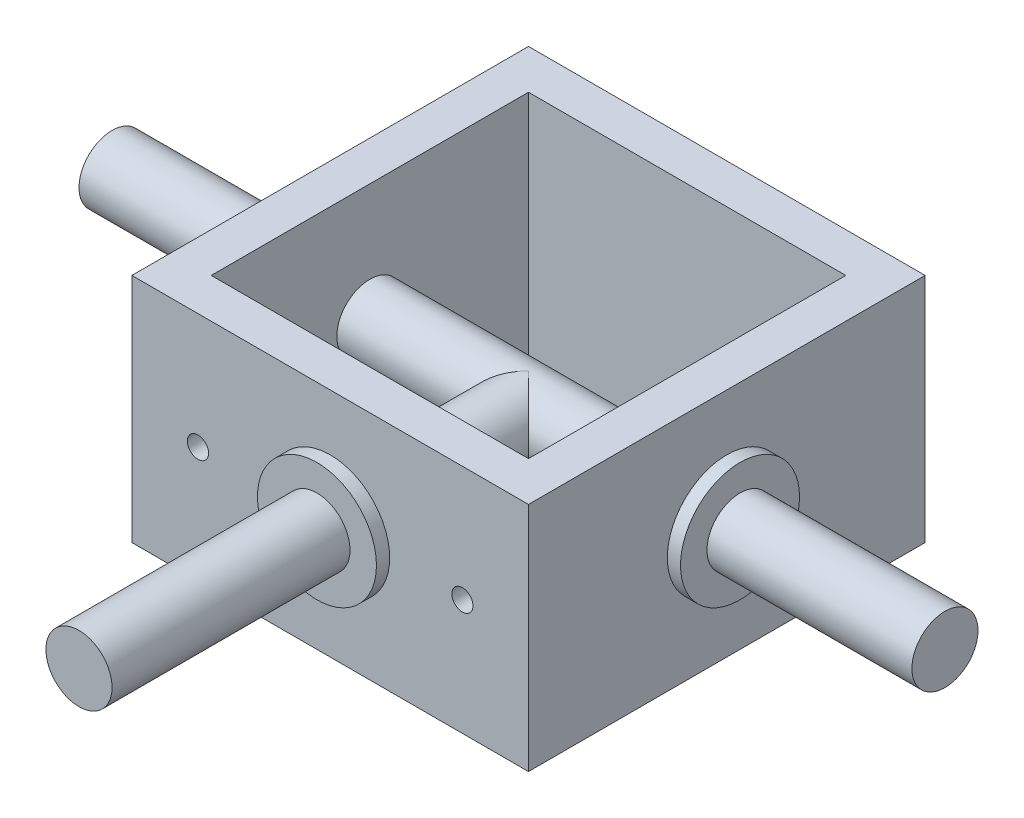
SolidWorks part; units mm, degrees
ref_plane "Alzado" through (0, 0, 0) normal (0, 0, 1) x (1, 0, 0)
ref_plane "Planta" through (0, 0, 0) normal (0, 1, 0) x (1, 0, 0)
ref_plane "Vista lateral" through (0, 0, 0) normal (1, 0, 0) x (0, 0, -1)
sketch "Croquis1" plane through (0, 0, 0) normal (0, 1, 0) x (1, 0, 0)
  line L1 (-30, 30) -> (30, 30)
  line L2 (-30, 30) -> (-30, -30)
  line L3 (-30, -30) -> (30, -30)
  line L4 (30, 30) -> (30, -30)
  line L5 (-30, 30) -> (30, -30) construction
  line L6 (-30, -30) -> (30, 30) construction
  line L7 (-24, -24) -> (24, -24)
  line L8 (-24, -24) -> (-24, 24)
  line L9 (-24, 24) -> (24, 24)
  line L10 (24, -24) -> (24, 24)
  point P0 (0, 0)
  dimension "D1" = 60
  dimension "D2" = 60
  dimension "D3" = 6
  dimension "D4" = 6
extrude "Saliente-Extruir1" add sketch "Croquis1" along normal blind 17.5 and the other way blind 17.5
sketch "Croquis2" plane through (0, 0, 30) normal (0, 0, 1) x (1, 0, 0)
  circle A0 centre (0, 0) radius 9
  dimension "D1" = 18
extrude "Saliente-Extruir2" add sketch "Croquis2" along normal blind 2
sketch "Croquis3" plane through (30, 0, 0) normal (1, 0, 0) x (0, 0, -1)
  circle A0 centre (0, 0) radius 9
  dimension "D1" = 18
extrude "Saliente-Extruir3" add sketch "Croquis3" along normal blind 2
sketch "Croquis4" plane through (-30, 0, 0) normal (-1, 0, 0) x (0, 0, 1)
  circle A0 centre (0, 0) radius 9
  dimension "D1" = 18
extrude "Saliente-Extruir4" add sketch "Croquis4" along normal blind 2
sketch "Croquis5" plane through (0, 0, 0) normal (1, 0, 0) x (0, 0, -1)
  circle A0 centre (0, 0) radius 5
  dimension "D1" = 10
extrude "Saliente-Extruir5" add sketch "Croquis5" along normal blind 63 and the other way blind 63
sketch "Croquis6" plane through (0, 0, 0) normal (0, 0, 1) x (1, 0, 0)
  circle A0 centre (0, 0) radius 5
  dimension "D1" = 10
extrude "Saliente-Extruir6" add sketch "Croquis6" along normal blind 68
sketch "Sketch1" plane through (0, 0, 30) normal (0, 0, 1) x (1, 0, 0)
  circle A0 centre (0, 0) radius 20 construction
  circle A1 centre (-20, 0) radius 1.6
  circle A2 centre (20, 0) radius 1.6
  dimension "D1" = 40
  dimension "D2" = 3.2
  dimension "D3" = 3.2
extrude "Cut-Extrude1" cut sketch "Sketch1" against normal up to next
